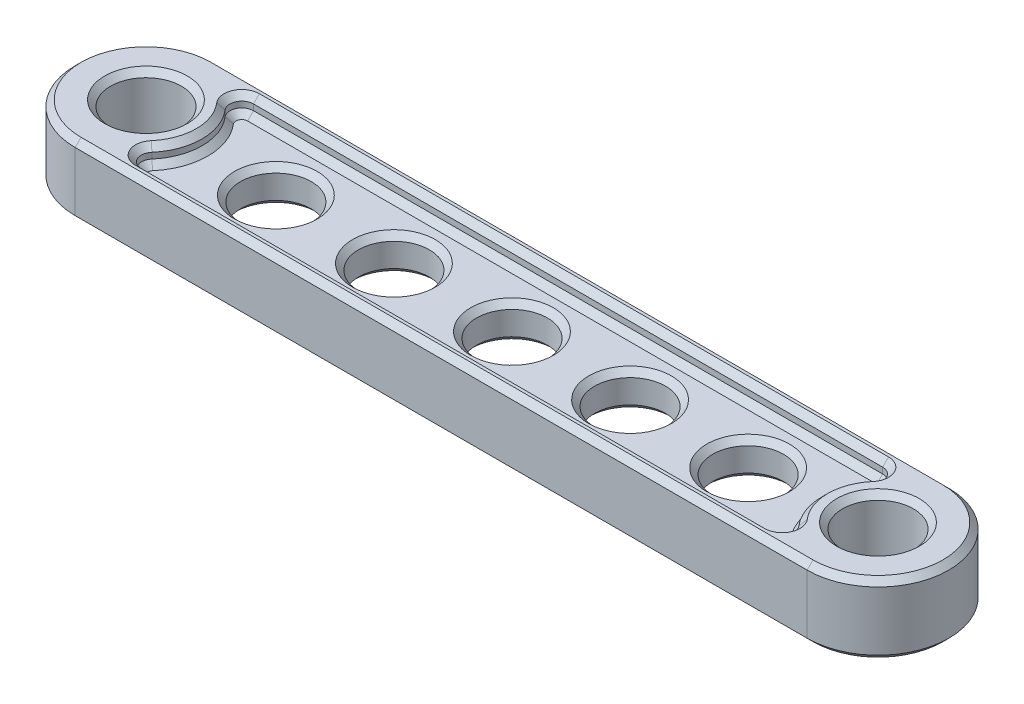
SolidWorks part; units mm, degrees
ref_plane "Front Plane" through (0, 0, 0) normal (0, 0, 1) x (1, 0, 0)
ref_plane "Top Plane" through (0, 0, 0) normal (0, 1, 0) x (1, 0, 0)
ref_plane "Right Plane" through (0, 0, 0) normal (1, 0, 0) x (0, 0, -1)
sketch "Sketch1" plane through (0, 0, 0) normal (0, 1, 0) x (1, 0, 0)
  line L0 (-31, 0) -> (31, 0) construction
  line L1 (-31, 0) -> (31, 0) construction
  line L2 (-31, 6) -> (31, 6)
  line L3 (-31, -6) -> (31, -6)
  line L4 (0, 16.6073) -> (0, -17.2952) construction
  arc A0 (-31, 6) -> (-31, -6) centre (-31, 0) ccw
  arc A1 (31, -6) -> (31, 6) centre (31, 0) ccw
  circle A2 centre (-31, 0) radius 3
  circle A3 centre (31, 0) radius 3
  circle A4 centre (0, 0) radius 3
  circle A5 centre (10, 0) radius 3
  circle A6 centre (20, 0) radius 3
  circle A7 centre (-20, 0) radius 3
  circle A8 centre (-10, 0) radius 3
  point P3 (0, 0)
  point P4 (0, 0)
  dimension "D1" = 6
  dimension "D3" = 6
  dimension "D4" = 6
  dimension "D2" = 62
  dimension "D6" = 10
  dimension "D5" = 3
extrude "Boss-Extrude1" add sketch "Sketch1" along normal mid plane 6
sketch "Sketch2" plane through (0, 0, 0) normal (0, 1, 0) x (1, 0, 0)
  line L0 (0, 15.3362) -> (0, -17.418) construction
  line L1 (-26.6411, 4.75) -> (26.6411, 4.75)
  line L2 (-31, 0) -> (31, 0) construction
  line L3 (-26.6411, -4.75) -> (26.6411, -4.75)
  arc A0 (-27.3992, -3.0978) -> (-27.3992, 3.0978) centre (-31, 0) ccw
  arc A1 (27.3992, -3.0978) -> (27.3992, 3.0978) centre (31, 0) cw
  arc A2 (-26.6411, 4.75) -> (-27.3992, 3.0978) centre (-26.6411, 3.75) ccw
  arc A3 (-26.6411, -4.75) -> (-27.3992, -3.0978) centre (-26.6411, -3.75) cw
  arc A4 (26.6411, -4.75) -> (27.3992, -3.0978) centre (26.6411, -3.75) ccw
  arc A5 (26.6411, 4.75) -> (27.3992, 3.0978) centre (26.6411, 3.75) cw
  point P12 (-31, 4.75)
  point P15 (-31, -4.75)
  point P18 (31, -4.75)
  point P21 (31, 4.75)
  dimension "D1" = 9.5
  dimension "D3" = 1
  dimension "D2" = 9.5
extrude "Cut-Extrude1" cut sketch "Sketch2" along normal blind 6 from offset 1.5
extrude "Cut-Extrude2" cut sketch "Sketch2<2>" against normal blind 6 from offset 1.5 offset against normal yes
sketch "Sketch2<2>" plane through (0, 0, 0) normal (0, 1, 0) x (1, 0, 0) same geometry as "Sketch2"
chamfer "Chamfer1" distance 0.5 angle 45 54 edges at (-26.25, -1.5, 0) (-27.55, -1.5, 4.167) (0, -1.5, 4.75) (27.55, -1.5, 4.167) (26.25, -1.5, 0) (27.55, -1.5, -4.167) (0, -1.5, -4.75) (-27.55, -1.5, -4.167) (-10, -1.5, 3) (-20, -1.5, 3) (20, -1.5, 3) (10, -1.5, 3) (0, -1.5, 3) (0, 1.5, -4.75) (27.55, 1.5, -4.167) (26.25, 1.5, 0) (27.55, 1.5, 4.167) (0, 1.5, 4.75) (-27.55, 1.5, 4.167) (-26.25, 1.5, 0) (-27.55, 1.5, -4.167) (-10, 1.5, 3) (-20, 1.5, 3) (20, 1.5, 3) (10, 1.5, 3) (0, 1.5, 3) (27.55, -3, -4.167) (26.25, -3, 0) (27.55, -3, 4.167) (0, -3, 4.75) (-27.55, -3, 4.167) (-26.25, -3, 0) (-27.55, -3, -4.167) (0, -3, -4.75) (0, -3, 6) (37, -3, 0) (0, -3, -6) (-37, -3, 0) (-31, -3, 3) (31, -3, -3) (-27.55, 3, 4.167) (0, 3, 4.75) (27.55, 3, 4.167) (26.25, 3, 0) (27.55, 3, -4.167) (0, 3, -4.75) (-27.55, 3, -4.167) (-26.25, 3, 0) (31, 3, -3) (0, 3, -6) (37, 3, 0) (0, 3, 6) (-37, 3, 0) (-31, 3, 3)
